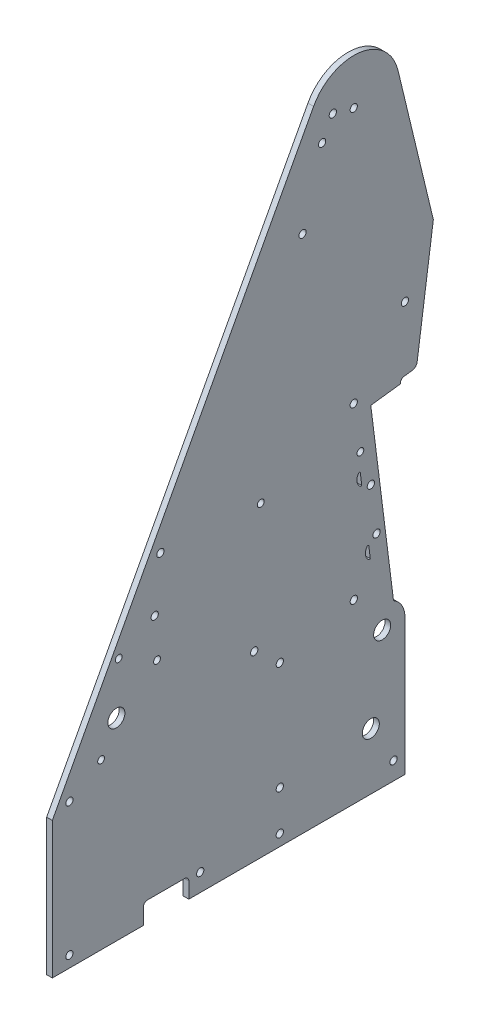
SolidWorks part; units mm, degrees
ref_plane "Front Plane" through (0, 0, 0) normal (0, 0, 1) x (1, 0, 0)
ref_plane "Top Plane" through (0, 0, 0) normal (0, 1, 0) x (1, 0, 0)
ref_plane "Right Plane" through (0, 0, 0) normal (1, 0, 0) x (0, 0, -1)
sketch "Sketch1" plane through (0, 0, 0) normal (1, 0, 0) x (0, 0, -1)
  line L0 (0, 0) -> (0, 76.2)
  line L6 (-19.05, 188.0016) -> (-2.512, 190.0852)
  line L7 (6.4943, 193.62) -> (15.875, 260.35)
  line L8 (15.875, 260.35) -> (-3.8791, 342.4892)
  line L9 (-50.965, 348.5436) -> (-196.85, 76.2)
  line L10 (-196.85, 0) -> (0, 0)
  line L11 (-196.85, 76.2) -> (-196.85, 0)
  line L12 (-19.05, 188.0016) -> (-6.35, 87.1985)
  line L13 (-0.4471, 192.7455) -> (6.4943, 193.62)
  line L14 (-2.512, 190.0852) -> (-3.1086, 194.8203) construction
  line L15 (-2.512, 190.0852) -> (6.1508, 191.1766) construction
  line L16 (6.1508, 191.1766) -> (6.4943, 193.62) construction
  arc A0 (-3.8791, 342.4892) -> (-50.965, 348.5436) centre (-28.575, 336.55) ccw
  arc A3 (0, 76.2) -> (-6.35, 87.1985) centre (-12.7, 76.2) ccw
  arc A4 (-2.512, 190.0852) -> (-0.4471, 192.7455) centre (-0.1494, 190.3829) cw
  dimension "D2" = 25.4
  dimension "D6" = 196.85
  dimension "D7" = 76.2
  dimension "D12" = 12.7
  dimension "D8" = 19.05
  dimension "D10" = 2.3813
  dimension "D1" = 28.575
  dimension "D3" = 336.55
  dimension "D4" = 25.4
  dimension "D5" = 101.6
  dimension "D9" = 6.35
  dimension ".5" = 12.7
  dimension "D11" = 76.2
  dimension "D13" = 76.2
  dimension "D14" = 15.875
  dimension "D15" = 6.35
extrude "Boss-Extrude1" add sketch "Sketch1" along normal blind 3.175
sketch "Sketch2" plane through (3.175, 0, 0) normal (1, 0, 0) x (0, 0, -1)
  line L16 (-146.05, 8.7909) -> (-146.05, -0.3034) construction
  line L17 (-123.0376, 11.1785) -> (-143.6624, 11.1785) construction
  line L18 (-120.65, -0.3034) -> (-120.65, 8.7909) construction
  line L19 (-146.05, 8.7909) -> (-146.05, 0)
  line L20 (-123.0376, 11.1785) -> (-143.6624, 11.1785)
  line L21 (-120.65, 0) -> (-120.65, 8.7909)
  line L25 (-146.05, 0) -> (-120.65, 0)
  line L26 (-196.85, 0) -> (0, 0) construction
  line L33 (-223.2996, 0) -> (-223.2996, 6.35) construction
  line L34 (-229.6496, 0) -> (-223.2996, 0) construction
  line L35 (-229.6496, 6.35) -> (-229.6496, 0) construction
  line L36 (-223.2996, 6.35) -> (-229.6496, 6.35) construction
  line L37 (-223.2996, 0) -> (-223.2996, 6.35)
  line L38 (-229.6496, 0) -> (-223.2996, 0)
  line L39 (-229.6496, 6.35) -> (-229.6496, 0)
  line L40 (-223.2996, 6.35) -> (-229.6496, 6.35)
  arc A0 (-143.6624, 11.1785) -> (-146.05, 8.7909) centre (-143.6624, 8.7909) ccw construction
  arc A1 (-120.65, 8.7909) -> (-123.0376, 11.1785) centre (-123.0376, 8.7909) ccw construction
  arc A2 (-143.6624, 11.1785) -> (-146.05, 8.7909) centre (-143.6624, 8.7909) ccw
  arc A3 (-120.65, 8.7909) -> (-123.0376, 11.1785) centre (-123.0376, 8.7909) ccw
extrude "Cut-Extrude1" cut sketch "Sketch2" against normal through all
sketch "Sketch3" plane through (3.175, 0, 0) normal (1, 0, 0) x (0, 0, -1)
  point P4 (-12.7, 76.2)
hole_wizard "3/8 Clearance Hole1" positions "Sketch3" profile "Sketch4" hole size "3/8" standard "ANSI Inch" end condition up to next
sketch "Sketch4" plane through (3.175, 76.2, 12.7) normal (0, 1, 0) x (0, 0, -1)
  line L0 (0, 0) -> (0, 3.175)
  line L1 (0, 3.175) -> (4.7625, 3.175)
  line L2 (4.7625, 3.175) -> (4.7625, 0)
  line L5 (4.7625, 0) -> (0, 0)
  line L11 (0, -6.35) -> (0, 107.95) construction
  dimension "Thru Hole Dia." = 9.525
  dimension "Thru Hole Depth" = 3.175
sketch "Sketch5" plane through (3.175, 0, 0) normal (1, 0, 0) x (0, 0, -1)
  line L0 (-12.7, 76.2) -> (19.6681, 37.0472)
  line L1 (19.6681, 37.0472) -> (18.4836, 24.56)
  line L2 (15.6221, 41.9413) -> (-25.2806, 17.5464)
  line L3 (-15.875, 19.05) -> (-25.2806, 17.5464)
  line L4 (0, 0) -> (0, 76.2) construction
  line L5 (-15.875, 19.05) -> (-27.0501, 3.6221)
  line L6 (-27.0501, 3.6221) -> (-54.7505, 169.5016)
  line L7 (50.8, 0) -> (50.8, 73.5762) construction
  dimension "D1" = 44.45
  dimension "D2" = 50.8
  dimension "D3" = 45
  dimension "D4" = 60.325
  dimension "D5" = 19.05
  dimension "D6" = 15.875
  dimension "D7" = 9.525
  dimension "D8" = 47.625
  dimension "D9" = 19.05
  dimension "D10" = 45
  dimension "D11" = 50.8
sketch "Sketch6" plane through (3.175, 0, 0) normal (1, 0, 0) x (0, 0, -1)
  circle A3 centre (-161.1018, 107.8367) radius 4.7625
  circle A5 centre (-161.1018, 107.8367) radius 6.985 construction
  circle A8 centre (-159.7995, 135.9536) radius 1.905 construction
  circle A9 centre (-138.417, 124.4998) radius 1.905 construction
  arc A10 (-167.9472, 91.0243) -> (-168.7477, 93.563) centre (-169.6472, 91.8837) ccw construction
  arc A11 (-168.7477, 93.563) -> (-171.3047, 92.8228) centre (-169.6472, 91.8837) ccw construction
  arc A12 (-171.3047, 92.8228) -> (-167.9472, 91.0243) centre (-169.6472, 91.8837) ccw construction
  circle A17 centre (-159.7995, 135.9536) radius 1.905
  circle A18 centre (-138.417, 124.4998) radius 1.905
  arc A19 (-167.9472, 91.0243) -> (-168.7477, 93.563) centre (-169.6472, 91.8837) ccw
  arc A20 (-168.7477, 93.563) -> (-171.3047, 92.8228) centre (-169.6472, 91.8837) ccw
  arc A21 (-171.3047, 92.8228) -> (-167.9472, 91.0243) centre (-169.6472, 91.8837) ccw
  dimension "D1" = 9.525
extrude "Cut-Extrude2" cut sketch "Sketch6" against normal through all
sketch "Sketch10" plane through (3.175, 0, 0) normal (1, 0, 0) x (0, 0, -1)
  circle A0 centre (-71.2566, 151.9429) radius 2.032
  dimension "D1" = 4.064
sketch "Sketch11" plane through (3.175, 0, 0) normal (1, 0, 0) x (0, 0, -1)
  circle A0 centre (-187.325, 80.5336) radius 2.032
  circle A1 centre (-187.325, 6.35) radius 2.032
  circle A2 centre (-187.325, 6.35) radius 2.032 construction
  circle A3 centre (-187.325, 80.5336) radius 2.032 construction
  dimension "D1" = 4.064
extrude "Cut-Extrude5" cut sketch "Sketch11" against normal through all
sketch "Sketch13" plane through (0, 0, 0) normal (-1, 0, 0) x (0, 0, 1)
  circle A0 centre (40.2353, 339.6611) radius 2.032
  circle A1 centre (46.232, 328.466) radius 2.032
  circle A2 centre (40.2353, 339.6611) radius 1.905 construction
  circle A3 centre (46.232, 328.466) radius 1.905 construction
  dimension "D1" = 4.064
extrude "Cut-Extrude6" cut sketch "Sketch13" against normal through all
sketch "Sketch14" plane through (3.175, 0, 0) normal (1, 0, 0) x (0, 0, -1)
  line L0 (-50.965, 348.5436) -> (-196.85, 76.2) construction
  line L1 (-136.525, 175.369) -> (-142.1225, 178.3674) construction
  circle A0 centre (-136.525, 175.369) radius 2.032
  dimension "D1" = 4.064
  dimension "D2" = 6.35
  dimension "D3" = 136.525
extrude "Cut-Extrude7" cut sketch "Sketch14" against normal through all
sketch "Sketch15" plane through (3.175, 0, 0) normal (1, 0, 0) x (0, 0, -1)
  circle A0 centre (-19.05, 31.75) radius 4.7625
  circle A1 centre (-12.7, 76.2) radius 4.7625 construction
  circle A2 centre (-28.575, 193.675) radius 2.032
  dimension "D1" = 44.45
  dimension "D3" = 4.064
  dimension "D2" = 6.35
  dimension "D4" = 161.925
  dimension "D5" = 9.525
extrude "Cut-Extrude8" cut sketch "Sketch15" against normal through all
sketch "Sketch16" plane through (3.175, 0, 0) normal (1, 0, 0) x (0, 0, -1)
  line L0 (-24.978, 158.8539) -> (-24.0851, 151.7662)
  line L1 (-6.35, 87.1985) -> (-19.05, 188.0016) construction
  line L2 (-20.2155, 121.0527) -> (-21.0031, 120.9535)
  line L3 (-24.978, 158.8539) -> (-25.7656, 158.7547)
  line L4 (-24.0851, 151.7662) -> (-24.8726, 151.667)
  line L5 (-12.7, 137.6001) -> (-26.6484, 135.8427) construction
  line L6 (-19.3226, 113.965) -> (-20.1101, 113.8658)
  line L7 (-19.3226, 113.965) -> (-20.2155, 121.0527)
  line L8 (-25.3253, 161.6102) -> (-23.7378, 149.0099) construction
  arc A0 (-25.7656, 158.7547) -> (-24.8726, 151.667) centre (-21.7352, 155.6624) ccw
  arc A1 (-20.1101, 113.8658) -> (-21.0031, 120.9535) centre (-16.9727, 117.8612) cw
  circle A2 centre (-19.0126, 149.6052) radius 2.032
  circle A3 centre (-15.8376, 124.4044) radius 2.032
  point P2 (-24.5315, 155.31)
  dimension "D2" = 0.7937
  dimension "D3" = 5.08
  dimension "D5" = 4.064
  dimension "D1" = 7.1437
  dimension "D4" = 38.1
  dimension "D6" = 4.7625
  dimension "D7" = 25.4
extrude "Cut-Extrude9" cut sketch "Sketch16" against normal up to next
fillet "Fillet1" radius 3.175 1 edges at (1.5875, 193.62, -6.4943)
sketch "Sketch17" plane through (3.175, 0, 0) normal (1, 0, 0) x (0, 0, -1)
  circle A0 centre (-6.35, 9.9085) radius 2.032
  circle A1 centre (-69.85, 6.35) radius 2.032
  circle A2 centre (-114.3, 9.9085) radius 2.032
  circle A3 centre (-114.3, 9.9085) radius 1.905 construction
  circle A4 centre (-69.85, 6.35) radius 2.286 construction
  circle A5 centre (-6.35, 9.9085) radius 1.905 construction
  circle A6 centre (-69.85, 28.575) radius 2.032
  circle A7 centre (-69.85, 28.575) radius 1.905 construction
  dimension "D1" = 4.064
extrude "Cut-Extrude10" cut sketch "Sketch17" against normal through all
sketch "Sketch18" plane through (0, 0, 0) normal (-1, 0, 0) x (0, 0, 1)
  line L0 (50.965, 348.5436) -> (196.85, 76.2) construction
  circle A0 centre (0, 228.6) radius 2.032
  circle A1 centre (69.85, 88.9) radius 2.032
  circle A2 centre (139.7, 146.5801) radius 2.032
  circle A3 centre (57.15, 289.9291) radius 2.032
  dimension "D1" = 4.064
  dimension "D2" = 228.6
  dimension "D4" = 17.145
  dimension "D5" = 139.7
  dimension "D6" = 22.225
  dimension "D7" = 57.15
  dimension "D8" = 69.85
  dimension "D9" = 88.9
extrude "Cut-Extrude11" cut sketch "Sketch18" against normal through all
sketch "Sketch19" plane through (0, 0, 0) normal (-1, 0, 0) x (0, 0, 1)
  circle A0 centre (28.575, 336.55) radius 2.032
  arc A1 (50.965, 348.5436) -> (3.8791, 342.4892) centre (28.575, 336.55) ccw construction
  dimension "D1" = 4.064
extrude "Cut-Extrude12" cut sketch "Sketch19" against normal through all
sketch "Sketch20" plane through (3.175, 0, 0) normal (1, 0, 0) x (0, 0, -1)
  line L0 (-84.1375, 101.6) -> (-28.5243, 98.6854) construction
  line L1 (-84.1375, 101.6) -> (-84.1375, 99.4903) construction
  circle A0 centre (-28.5243, 98.6854) radius 2.032
  circle A1 centre (-84.1375, 101.6) radius 2.032
  dimension "D2" = 4.064
  dimension "D1" = 55.6895
  dimension "D3" = 87
  dimension "D4" = 84.1375
  dimension "D5" = 101.6
extrude "Cut-Extrude13" cut sketch "Sketch20" against normal through all
sketch "Sketch22" plane through (3.175, 0, 0) normal (1, 0, 0) x (0, 0, -1)
  circle A0 centre (-80.4818, 171.3543) radius 1.905
  circle A1 centre (-24.8687, 168.4397) radius 1.905
  point P5 (-79.5044, 172.1379)
  point P8 (-23.9417, 168.3831)
  dimension "D1" = 3.81
extrude "Cut-Extrude14" cut sketch "Sketch22" against normal blind 6.35
